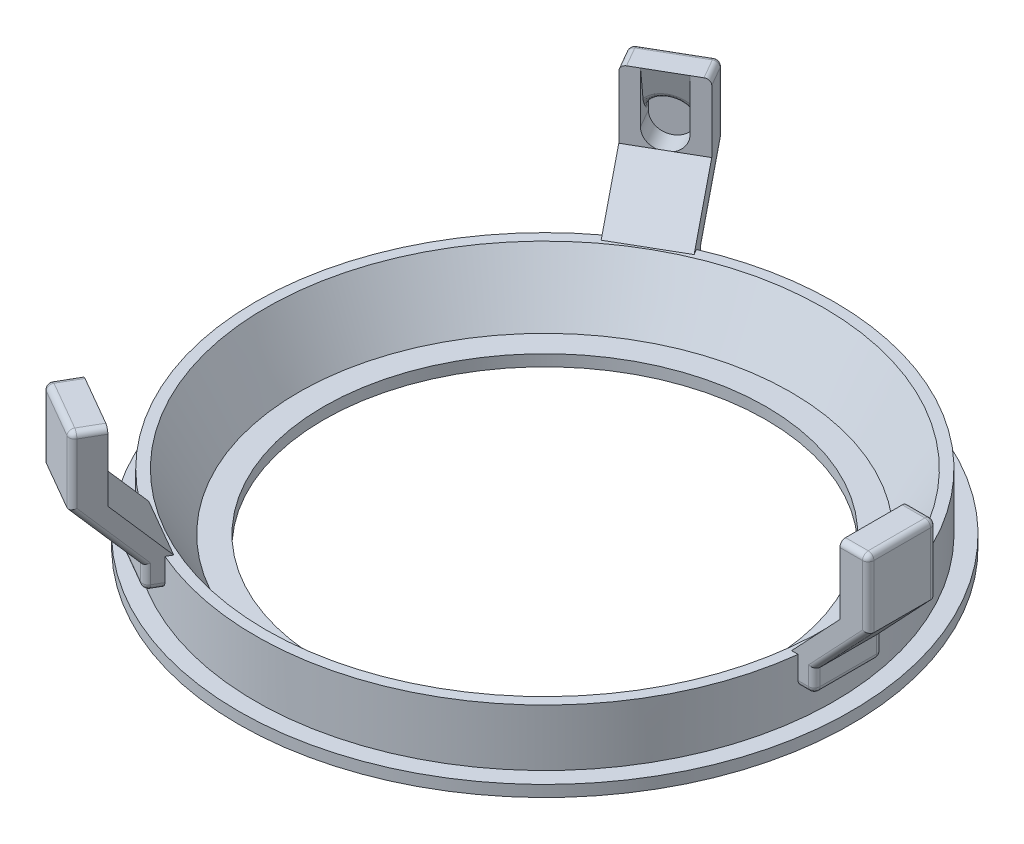
SolidWorks part; units mm, degrees
ref_plane "Front Plane" through (0, 0, 0) normal (0, 0, 1) x (1, 0, 0)
ref_plane "Top Plane" through (0, 0, 0) normal (0, 1, 0) x (1, 0, 0)
ref_plane "Right Plane" through (0, 0, 0) normal (1, 0, 0) x (0, 0, -1)
sketch "Sketch2" plane through (0, 0, 0) normal (0, 0, 1) x (1, 0, 0)
  line L3 (-24.5868, 6) -> (-21.7, 1)
  line L5 (-25.5, 6) -> (-24.5868, 6)
  line L6 (0, 0) -> (0, 5) construction
  line L7 (-25.5, 6) -> (-25.5, 1)
  line L8 (-25.5, 1) -> (-27, 1)
  line L9 (-27, 1) -> (-27, 0)
  line L15 (-21.7, 1) -> (-19.5, 1)
  line L16 (-19.5, 1) -> (-19.5, 0)
  line L17 (-19.5, 0) -> (-27, 0)
  dimension "D1" = 1
  dimension "D2" = 21.7
  dimension "D3" = 27
  dimension "D4" = 1.5
  dimension "D5" = 5
  dimension "D6" = 120
  dimension "D7" = 19.5
revolve "Revolve1" add sketch "Sketch2" angle 360 about L6
sketch "Sketch3" plane through (0, 0, 0) normal (0, 0, 1) x (1, 0, 0)
  line L5 (27, 1) -> (-27, 1) construction
  line L10 (29, 12) -> (29, 16.5)
  line L11 (29, 16.5) -> (31.5, 16.5)
  line L12 (31.5, 16.5) -> (31.5, 10.5)
  line L13 (24.75, 6) -> (24.75, 1) construction
  line L14 (25.5, 6) -> (-25.5, 6) construction
  line L15 (25.5, 1) -> (-25.5, 1) construction
  line L16 (31.5, 10.5) -> (26.75, 5.4706)
  line L17 (29, 12) -> (29, 10.5)
  line L18 (26.75, 5.4706) -> (26.75, 3.5)
  line L19 (26.75, 3.5) -> (24.75, 3.5)
  line L20 (29, 10.5) -> (24.75, 6)
  line L21 (24.75, 6) -> (24.75, 3.5)
  point P8 (29, 12)
  dimension "D1" = 29
  dimension "D2" = 11
  dimension "D3" = 2.5
  dimension "D4" = 2.5
  dimension "D5" = 2
  dimension "D6" = 24.75
  dimension "D7" = 1.5
  dimension "D8" = 4.5
extrude "Boss-Extrude1" add sketch "Sketch3" along normal blind 3 and the other way blind 3
sketch "Sketch4" plane through (29, 0, 0) normal (-1, 0, 0) x (0, 0, 1)
  line L0 (25.5, 1) -> (-25.5, 1) construction
  line L1 (0, 12) -> (0, 12.5) construction
  line L2 (-1.6, 12) -> (-1.6, 12.5)
  line L3 (1.6, 12) -> (1.6, 12.5)
  arc A1 (-1.6, 12) -> (1.6, 12) centre (0, 12) ccw
  arc A2 (1.6, 12.5) -> (-1.6, 12.5) centre (0, 12.5) ccw
  point P4 (0, 12.25)
  dimension "D3" = 1.6
  dimension "D1" = 11
  dimension "D4" = 0.25
extrude "Cut-Extrude1" cut sketch "Sketch4" against normal blind 1.9
sketch "Sketch5" plane through (0, 0, 3) normal (0, 0, 1) x (1, 0, 0)
  line L0 (29, 16.5) -> (30, 12)
  line L1 (30, 12) -> (29, 12)
  line L2 (29, 16.5) -> (29, 10.5) construction
  line L3 (29, 16.5) -> (29, 12)
  dimension "D1" = 4.5
  dimension "D2" = 1
extrude "Cut-Extrude2" cut sketch "Sketch5" against normal blind 3.2 from offset 1.4 offset against normal yes
fillet "Fillet1" radius 0.5 1 edges at (29.5333, 14.1, 0)
fillet "Fillet2" radius 0.5 9 edges at (26.0365, 3.5, -3) (26.75, 4.4853, -3) (29.125, 7.9853, -3) (31.5, 13.5, -3) (31.5, 16.5, 0) (31.5, 13.5, 3) (29.125, 7.9853, 3) (26.75, 4.4853, 3) (26.0365, 3.5, 3)
fillet "Fillet3" radius 0.5 3 edges at (26.6036, 3.6464, -2.8536) (26.6036, 3.6464, 2.8536) (26.75, 3.5, 0)
fillet "Fillet4" radius 0.5 4 edges at (31.3536, 16.3536, 2.8536) (31.3536, 16.3536, -2.8536) (30, 16.5, 3) (30, 16.5, -3)
pattern_circular "CirPattern1" count 3 over 360 about axis through (0, 6, 0) along (0, -1, 0) of "Boss-Extrude1", "Cut-Extrude1", "Cut-Extrude2", "Fillet1", "Fillet2", "Fillet3", "Fillet4"
